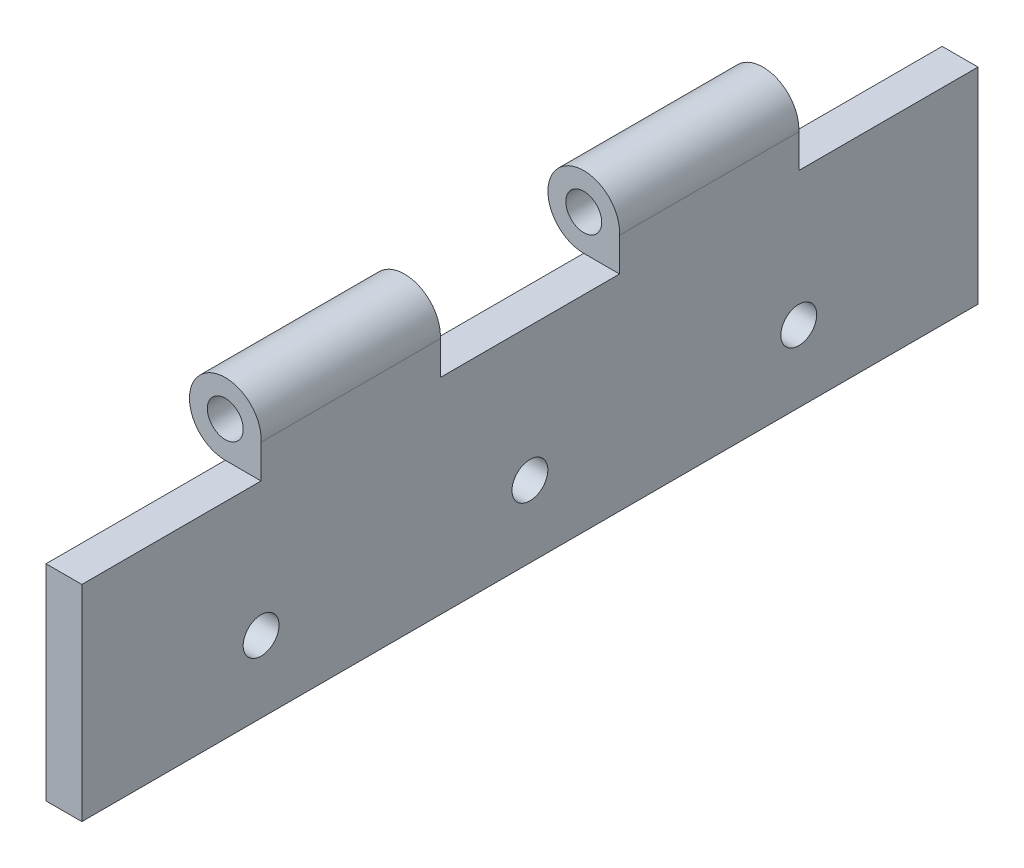
SolidWorks part; units mm, degrees
ref_plane "Front" through (0, 0, 0) normal (0, 0, 1) x (1, 0, 0)
ref_plane "Top" through (0, 0, 0) normal (0, 1, 0) x (1, 0, 0)
ref_plane "Right" through (0, 0, 0) normal (1, 0, 0) x (0, 0, -1)
sketch "Sketch1" plane through (0, 0, 0) normal (0, 0, 1) x (1, 0, 0)
  line L0 (-2, 7.7697) -> (-2, -9.4231)
  line L1 (1, -9.4231) -> (-2, -9.4231)
  line L2 (1, -9.4231) -> (1, 10.5769)
  line L5 (1, -9.4231) -> (-0.4015, 10.6324) construction
  line L6 (1, 10.5769) -> (-2, -9.4231) construction
  arc A0 (1, 10.5769) -> (-2, 7.7697) centre (-1.9938, 10.7697) ccw
  circle A2 centre (-1.9938, 10.7697) radius 1.5
  point P0 (0.0465, 4.2206)
  dimension "D3" = 3
  dimension "D1" = 3
  dimension "D2" = 20
extrude "Boss-Extrude1" add sketch "Sketch1" along normal blind 37.5 and the other way blind 37.5
sketch "Sketch2" plane through (-2, 0, 0) normal (-1, 0, 0) x (0, 0, 1)
  line L0 (-37.5, 13.7697) -> (-37.5, 7.7697) construction
  line L1 (-37.5, 22.7697) -> (-22.5, 22.7697)
  line L2 (-37.5, 22.7697) -> (-37.5, 7.7697)
  line L3 (-37.5, 7.7697) -> (-22.5, 7.7697)
  line L4 (-22.5, 22.7697) -> (-22.5, 7.7697)
  line L5 (-37.5, 22.7697) -> (-22.5, 7.7697) construction
  line L6 (-37.5, 7.7697) -> (-22.5, 22.7697) construction
  line L7 (-7.5, 22.7697) -> (7.5, 22.7697)
  line L8 (-7.5, 22.7697) -> (-7.5, 7.7697)
  line L9 (-7.5, 7.7697) -> (7.5, 7.7697)
  line L10 (7.5, 22.7697) -> (7.5, 7.7697)
  line L11 (-7.5, 22.7697) -> (7.5, 7.7697) construction
  line L12 (-7.5, 7.7697) -> (7.5, 22.7697) construction
  line L13 (22.5, 22.7697) -> (37.5, 22.7697)
  line L14 (22.5, 22.7697) -> (22.5, 7.7697)
  line L15 (22.5, 7.7697) -> (37.5, 7.7697)
  line L16 (37.5, 22.7697) -> (37.5, 7.7697)
  line L17 (22.5, 22.7697) -> (37.5, 7.7697) construction
  line L18 (22.5, 7.7697) -> (37.5, 22.7697) construction
  line L20 (-37.5, 7.7697) -> (37.5, 7.7697) construction
  line L21 (-37.5, -9.4231) -> (37.5, -9.4231) construction
  circle A0 centre (-22.5, -3.4231) radius 1.5
  circle A1 centre (0, -3.4231) radius 1.5
  circle A2 centre (22.5, -3.4231) radius 1.5
  point P0 (-30, 15.2697)
  point P5 (0, 15.2697)
  point P10 (30, 15.2697)
  point P26 (6.2119, 7.7697)
  point P29 (-22.5, 7.7697)
  dimension "D7" = 6
  dimension "D1" = 15
  dimension "D2" = 15
  dimension "D3" = 15
  dimension "D4" = 15
  dimension "D5" = 15
  dimension "D6" = 15
  dimension "D8" = 6
  dimension "D9" = 6
  dimension "D10" = 7.5
extrude "Cut-Extrude1" cut sketch "Sketch2" against normal blind 37.5 and the other way blind 37.5
